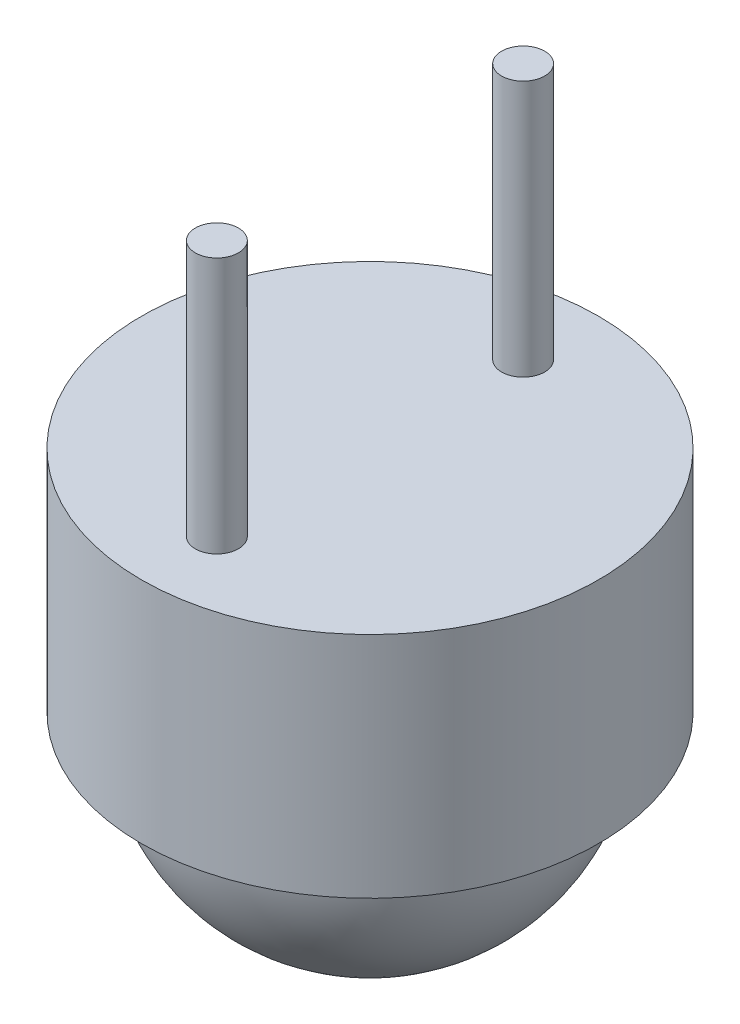
SolidWorks part; units mm, degrees
ref_plane "Front Plane" through (0, 0, 0) normal (0, 0, 1) x (1, 0, 0)
ref_plane "Top Plane" through (0, 0, 0) normal (0, 1, 0) x (1, 0, 0)
ref_plane "Right Plane" through (0, 0, 0) normal (1, 0, 0) x (0, 0, -1)
sketch "Sketch1" plane through (0, 0, 0) normal (0, 0, 1) x (1, 0, 0)
  line L0 (0, -9.525) -> (0, 9.525)
  arc A0 (0, -9.525) -> (0, 9.525) centre (0, 0) ccw
  dimension "D1" = 19.05
revolve "Metal Ball 3/4\"" add sketch "Sketch1" angle 360 about L0
sketch "Sketch2" plane through (0, 0, 0) normal (0, 1, 0) x (1, 0, 0)
  circle A0 centre (0, 0) radius 9.525
  circle A1 centre (0, 0) radius 11.557
  dimension "D1" = 2.032
extrude "Housing Pt. 1" add sketch "Sketch2" along normal blind 9.525 separate body
sketch "Sketch3" plane through (0, 9.525, 0) normal (0, 1, 0) x (1, 0, 0)
  circle A0 centre (0, 0) radius 11.557
extrude "Housing Pt. 2" add sketch "Sketch3" along normal blind 2.032
sketch "Sketch4" plane through (0, 11.557, 0) normal (0, 1, 0) x (1, 0, 0)
  line L0 (0, -7.747) -> (0, 7.747) construction
  circle A0 centre (0, 7.747) radius 1.09
  circle A1 centre (0, -7.747) radius 1.09
  point P5 (0, 0)
  dimension "D2" = 2.18
  dimension "D1" = 15.494
extrude "Screw Holes" cut sketch "Sketch4" against normal up to next (2.032 mm away)
sketch "Sketch5" plane through (0, 9.525, 0) normal (0, -1, 0) x (1, 0, 0)
  circle A0 centre (0, 7.747) radius 1.09
  circle A1 centre (0, -7.747) radius 1.09
  dimension "D1" = 2.18
extrude "Screws" add sketch "Sketch5" against normal blind 15 separate body
